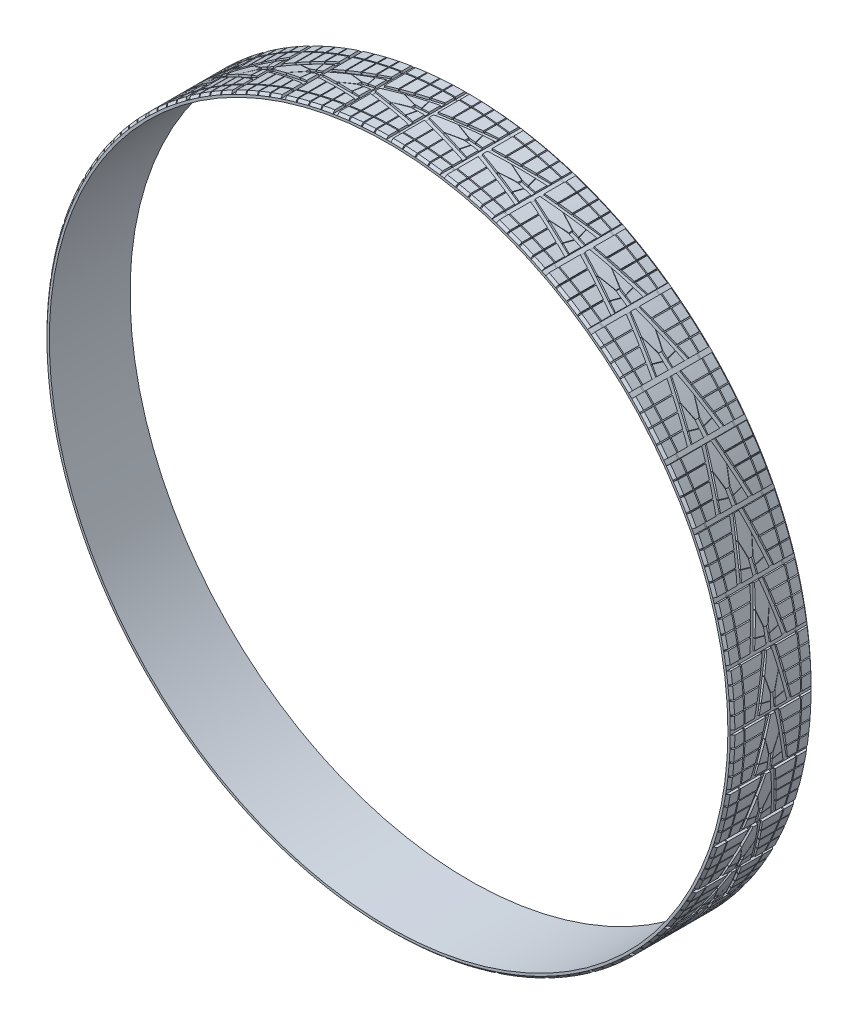
SolidWorks part; units mm, degrees
ref_plane "前视基准面" through (0, 0, 0) normal (0, 0, 1) x (1, 0, 0)
ref_plane "上视基准面" through (0, 0, 0) normal (0, 1, 0) x (1, 0, 0)
ref_plane "右视基准面" through (0, 0, 0) normal (1, 0, 0) x (0, 0, -1)
other "Configuration Table"
sketch "草图1" plane through (0, 0, 0) normal (0, 0, 1) x (1, 0, 0)
  circle A0 centre (0, 0) radius 147
  dimension "D1" = 294
extrude "拉伸-薄壁1" add sketch "草图1" along normal blind 35 thin
chamfer "倒角1" distance 1 angle 45 2 edges at (149, 0, 0) (149, 0, 35)
sketch "草图2" plane through (0, 0, 0) normal (0, 0, -1) x (-1, 0, 0)
  line L0 (0, 0) -> (0, 112.703) construction
  line L1 (-1, 148) -> (1, 148)
  line L2 (1, 148) -> (1, 150)
  line L3 (1, 150) -> (-1, 150)
  line L4 (-1, 150) -> (-1, 148)
  line L5 (22.4775, 148.3097) -> (22.1646, 146.3343)
  line L6 (22.1646, 146.3343) -> (24.14, 146.0214)
  line L7 (24.14, 146.0214) -> (24.4529, 147.9968)
  line L8 (24.4529, 147.9968) -> (22.4775, 148.3097)
  line L9 (45.4015, 142.9675) -> (44.7835, 141.0654)
  line L10 (44.7835, 141.0654) -> (46.6856, 140.4473)
  line L11 (46.6856, 140.4473) -> (47.3036, 142.3495)
  line L12 (47.3036, 142.3495) -> (45.4015, 142.9675)
  line L13 (67.2076, 134.105) -> (66.2996, 132.323)
  line L14 (66.2996, 132.323) -> (68.0816, 131.415)
  line L15 (68.0816, 131.415) -> (68.9896, 133.197)
  line L16 (68.9896, 133.197) -> (67.2076, 134.105)
  line L17 (87.3588, 121.9403) -> (86.1832, 120.3223)
  line L18 (86.1832, 120.3223) -> (87.8012, 119.1467)
  line L19 (87.8012, 119.1467) -> (88.9768, 120.7648)
  line L20 (88.9768, 120.7648) -> (87.3588, 121.9403)
  line L21 (105.3589, 106.7731) -> (103.9447, 105.3589)
  line L22 (103.9447, 105.3589) -> (105.3589, 103.9447)
  line L23 (105.3589, 103.9447) -> (106.7731, 105.3589)
  line L24 (106.7731, 105.3589) -> (105.3589, 106.7731)
  line L25 (120.7648, 88.9768) -> (119.1467, 87.8012)
  line L26 (119.1467, 87.8012) -> (120.3223, 86.1832)
  line L27 (120.3223, 86.1832) -> (121.9403, 87.3588)
  line L28 (121.9403, 87.3588) -> (120.7648, 88.9768)
  line L29 (133.197, 68.9896) -> (131.415, 68.0816)
  line L30 (131.415, 68.0816) -> (132.323, 66.2996)
  line L31 (132.323, 66.2996) -> (134.105, 67.2076)
  line L32 (134.105, 67.2076) -> (133.197, 68.9896)
  line L33 (142.3495, 47.3036) -> (140.4473, 46.6856)
  line L34 (140.4473, 46.6856) -> (141.0654, 44.7835)
  line L35 (141.0654, 44.7835) -> (142.9675, 45.4015)
  line L36 (142.9675, 45.4015) -> (142.3495, 47.3036)
  line L37 (147.9968, 24.4529) -> (146.0214, 24.14)
  line L38 (146.0214, 24.14) -> (146.3343, 22.1646)
  line L39 (146.3343, 22.1646) -> (148.3097, 22.4775)
  line L40 (148.3097, 22.4775) -> (147.9968, 24.4529)
  line L41 (150, 1) -> (148, 1)
  line L42 (148, 1) -> (148, -1)
  line L43 (148, -1) -> (150, -1)
  line L44 (150, -1) -> (150, 1)
  line L45 (148.3097, -22.4775) -> (146.3343, -22.1646)
  line L46 (146.3343, -22.1646) -> (146.0214, -24.14)
  line L47 (146.0214, -24.14) -> (147.9968, -24.4529)
  line L48 (147.9968, -24.4529) -> (148.3097, -22.4775)
  line L49 (142.9675, -45.4015) -> (141.0654, -44.7835)
  line L50 (141.0654, -44.7835) -> (140.4473, -46.6856)
  line L51 (140.4473, -46.6856) -> (142.3495, -47.3036)
  line L52 (142.3495, -47.3036) -> (142.9675, -45.4015)
  line L53 (134.105, -67.2076) -> (132.323, -66.2996)
  line L54 (132.323, -66.2996) -> (131.415, -68.0816)
  line L55 (131.415, -68.0816) -> (133.197, -68.9896)
  line L56 (133.197, -68.9896) -> (134.105, -67.2076)
  line L57 (121.9403, -87.3588) -> (120.3223, -86.1832)
  line L58 (120.3223, -86.1832) -> (119.1467, -87.8012)
  line L59 (119.1467, -87.8012) -> (120.7648, -88.9768)
  line L60 (120.7648, -88.9768) -> (121.9403, -87.3588)
  line L61 (106.7731, -105.3589) -> (105.3589, -103.9447)
  line L62 (105.3589, -103.9447) -> (103.9447, -105.3589)
  line L63 (103.9447, -105.3589) -> (105.3589, -106.7731)
  line L64 (105.3589, -106.7731) -> (106.7731, -105.3589)
  line L65 (88.9768, -120.7648) -> (87.8012, -119.1467)
  line L66 (87.8012, -119.1467) -> (86.1832, -120.3223)
  line L67 (86.1832, -120.3223) -> (87.3588, -121.9403)
  line L68 (87.3588, -121.9403) -> (88.9768, -120.7648)
  line L69 (68.9896, -133.197) -> (68.0816, -131.415)
  line L70 (68.0816, -131.415) -> (66.2996, -132.323)
  line L71 (66.2996, -132.323) -> (67.2076, -134.105)
  line L72 (67.2076, -134.105) -> (68.9896, -133.197)
  line L73 (47.3036, -142.3495) -> (46.6856, -140.4473)
  line L74 (46.6856, -140.4473) -> (44.7835, -141.0654)
  line L75 (44.7835, -141.0654) -> (45.4015, -142.9675)
  line L76 (45.4015, -142.9675) -> (47.3036, -142.3495)
  line L77 (24.4529, -147.9968) -> (24.14, -146.0214)
  line L78 (24.14, -146.0214) -> (22.1646, -146.3343)
  line L79 (22.1646, -146.3343) -> (22.4775, -148.3097)
  line L80 (22.4775, -148.3097) -> (24.4529, -147.9968)
  line L81 (1, -150) -> (1, -148)
  line L82 (1, -148) -> (-1, -148)
  line L83 (-1, -148) -> (-1, -150)
  line L84 (-1, -150) -> (1, -150)
  line L85 (-22.4775, -148.3097) -> (-22.1646, -146.3343)
  line L86 (-22.1646, -146.3343) -> (-24.14, -146.0214)
  line L87 (-24.14, -146.0214) -> (-24.4529, -147.9968)
  line L88 (-24.4529, -147.9968) -> (-22.4775, -148.3097)
  line L89 (-45.4015, -142.9675) -> (-44.7835, -141.0654)
  line L90 (-44.7835, -141.0654) -> (-46.6856, -140.4473)
  line L91 (-46.6856, -140.4473) -> (-47.3036, -142.3495)
  line L92 (-47.3036, -142.3495) -> (-45.4015, -142.9675)
  line L93 (-67.2076, -134.105) -> (-66.2996, -132.323)
  line L94 (-66.2996, -132.323) -> (-68.0816, -131.415)
  line L95 (-68.0816, -131.415) -> (-68.9896, -133.197)
  line L96 (-68.9896, -133.197) -> (-67.2076, -134.105)
  line L97 (-87.3588, -121.9403) -> (-86.1832, -120.3223)
  line L98 (-86.1832, -120.3223) -> (-87.8012, -119.1467)
  line L99 (-87.8012, -119.1467) -> (-88.9768, -120.7648)
  line L100 (-88.9768, -120.7648) -> (-87.3588, -121.9403)
  line L101 (-105.3589, -106.7731) -> (-103.9447, -105.3589)
  line L102 (-103.9447, -105.3589) -> (-105.3589, -103.9447)
  line L103 (-105.3589, -103.9447) -> (-106.7731, -105.3589)
  line L104 (-106.7731, -105.3589) -> (-105.3589, -106.7731)
  line L105 (-120.7648, -88.9768) -> (-119.1467, -87.8012)
  line L106 (-119.1467, -87.8012) -> (-120.3223, -86.1832)
  line L107 (-120.3223, -86.1832) -> (-121.9403, -87.3588)
  line L108 (-121.9403, -87.3588) -> (-120.7648, -88.9768)
  line L109 (-133.197, -68.9896) -> (-131.415, -68.0816)
  line L110 (-131.415, -68.0816) -> (-132.323, -66.2996)
  line L111 (-132.323, -66.2996) -> (-134.105, -67.2076)
  line L112 (-134.105, -67.2076) -> (-133.197, -68.9896)
  line L113 (-142.3495, -47.3036) -> (-140.4473, -46.6856)
  line L114 (-140.4473, -46.6856) -> (-141.0654, -44.7835)
  line L115 (-141.0654, -44.7835) -> (-142.9675, -45.4015)
  line L116 (-142.9675, -45.4015) -> (-142.3495, -47.3036)
  line L117 (-147.9968, -24.4529) -> (-146.0214, -24.14)
  line L118 (-146.0214, -24.14) -> (-146.3343, -22.1646)
  line L119 (-146.3343, -22.1646) -> (-148.3097, -22.4775)
  line L120 (-148.3097, -22.4775) -> (-147.9968, -24.4529)
  line L121 (-150, -1) -> (-148, -1)
  line L122 (-148, -1) -> (-148, 1)
  line L123 (-148, 1) -> (-150, 1)
  line L124 (-150, 1) -> (-150, -1)
  line L125 (-148.3097, 22.4775) -> (-146.3343, 22.1646)
  line L126 (-146.3343, 22.1646) -> (-146.0214, 24.14)
  line L127 (-146.0214, 24.14) -> (-147.9968, 24.4529)
  line L128 (-147.9968, 24.4529) -> (-148.3097, 22.4775)
  line L129 (-142.9675, 45.4015) -> (-141.0654, 44.7835)
  line L130 (-141.0654, 44.7835) -> (-140.4473, 46.6856)
  line L131 (-140.4473, 46.6856) -> (-142.3495, 47.3036)
  line L132 (-142.3495, 47.3036) -> (-142.9675, 45.4015)
  line L133 (-134.105, 67.2076) -> (-132.323, 66.2996)
  line L134 (-132.323, 66.2996) -> (-131.415, 68.0816)
  line L135 (-131.415, 68.0816) -> (-133.197, 68.9896)
  line L136 (-133.197, 68.9896) -> (-134.105, 67.2076)
  line L137 (-121.9403, 87.3588) -> (-120.3223, 86.1832)
  line L138 (-120.3223, 86.1832) -> (-119.1467, 87.8012)
  line L139 (-119.1467, 87.8012) -> (-120.7648, 88.9768)
  line L140 (-120.7648, 88.9768) -> (-121.9403, 87.3588)
  line L141 (-106.7731, 105.3589) -> (-105.3589, 103.9447)
  line L142 (-105.3589, 103.9447) -> (-103.9447, 105.3589)
  line L143 (-103.9447, 105.3589) -> (-105.3589, 106.7731)
  line L144 (-105.3589, 106.7731) -> (-106.7731, 105.3589)
  line L145 (-88.9768, 120.7648) -> (-87.8012, 119.1467)
  line L146 (-87.8012, 119.1467) -> (-86.1832, 120.3223)
  line L147 (-86.1832, 120.3223) -> (-87.3588, 121.9403)
  line L148 (-87.3588, 121.9403) -> (-88.9768, 120.7648)
  line L149 (-68.9896, 133.197) -> (-68.0816, 131.415)
  line L150 (-68.0816, 131.415) -> (-66.2996, 132.323)
  line L151 (-66.2996, 132.323) -> (-67.2076, 134.105)
  line L152 (-67.2076, 134.105) -> (-68.9896, 133.197)
  line L153 (-47.3036, 142.3495) -> (-46.6856, 140.4473)
  line L154 (-46.6856, 140.4473) -> (-44.7835, 141.0654)
  line L155 (-44.7835, 141.0654) -> (-45.4015, 142.9675)
  line L156 (-45.4015, 142.9675) -> (-47.3036, 142.3495)
  line L157 (-24.4529, 147.9968) -> (-24.14, 146.0214)
  line L158 (-24.14, 146.0214) -> (-22.1646, 146.3343)
  line L159 (-22.1646, 146.3343) -> (-22.4775, 148.3097)
  line L160 (-22.4775, 148.3097) -> (-24.4529, 147.9968)
  point P166 (0, 0)
  dimension "D1" = 1
  dimension "D2" = 1
  dimension "D3" = 148
  dimension "D5" = 150
  dimension "D4" = 40
extrude "切除-拉伸1" cut sketch "草图2" against normal through all
ref_plane "基准面1" through (0, 0, 5) normal (0, 0, 1) x (1, 0, 0)
sketch "草图3" plane through (0, 0, 5) normal (0, 0, 1) x (1, 0, 0)
  circle A0 centre (0, 0) radius 149
  circle A1 centre (0, 0) radius 148
  dimension "D1" = 296
  dimension "D2" = 298
extrude "切除-拉伸2" cut sketch "草图3" along normal blind 0.5
ref_plane "基准面2" through (0, 0, 30) normal (0, 0, 1) x (1, 0, 0)
sketch "草图4" plane through (0, 0, 30) normal (0, 0, 1) x (1, 0, 0)
  circle A0 centre (0, 0) radius 149
  circle A1 centre (0, 0) radius 148
  dimension "D1" = 298
extrude "切除-拉伸3" cut sketch "草图4" against normal blind 0.5
sketch3d "3D草图1"
  point P0 (148.5567, -11.4847, 15.2513)
ref_plane "基准面3" through (148.583, -11.1348, 0) normal (0.9972, -0.0747, 0) x (0.0747, 0.9972, 0)
sketch "草图5" plane through (148.583, -11.1348, 0) normal (0.9972, -0.0747, 0) x (0.0747, 0.9972, 0)
  line L0 (10.1373, 17.5) -> (-11.1671, 17.5) construction
  line L1 (10.1373, 5.5) -> (10.1373, 29.5) construction
  line L2 (-11.1671, 29.5) -> (-11.1671, 5.5) construction
  line L3 (-11.249, 25.5) -> (10.1373, 20.5)
  line L4 (-11.249, 29.5) -> (-11.249, 5.5) construction
  line L5 (10.1373, 20.5) -> (10.1373, 18.5)
  line L6 (10.1373, 18.5) -> (-11.249, 23.5)
  line L7 (-11.249, 23.5) -> (-11.249, 25.5)
  line L8 (10.1373, 16.5) -> (-11.249, 11.5)
  line L9 (10.1373, 14.5) -> (10.1373, 16.5)
  line L10 (-11.249, 9.5) -> (10.1373, 14.5)
  line L11 (-11.249, 11.5) -> (-11.249, 9.5)
  line L12 (-11.249, 18.5) -> (-5.249, 18.5)
  line L13 (-5.249, 18.5) -> (-5.249, 16.5)
  line L14 (-5.249, 16.5) -> (-11.249, 16.5)
  line L15 (-11.249, 18.5) -> (-11.249, 16.5)
  dimension "D1" = 2
  dimension "D2" = 1
  dimension "D3" = 6
  dimension "D4" = 1
  dimension "D5" = 6
extrude "切除-拉伸4" cut sketch "草图5" against normal mid plane 2
sketch "草图6" plane through (148.583, -11.1348, 0) normal (0.9972, -0.0747, 0) x (0.0747, 0.9972, 0)
  line L0 (-5.249, 18.5) -> (1.476, 20.525)
  line L1 (-11.2015, 23.4889) -> (10.0882, 18.5115) construction
  line L2 (1.476, 20.525) -> (1.6707, 20.4794)
  line L3 (10.1373, 18.5) -> (-11.249, 23.5) construction
  line L4 (1.6707, 20.4794) -> (-5.249, 18.3)
  line L5 (-5.249, 16.5) -> (-5.249, 18.5) construction
  line L6 (-5.249, 18.3) -> (-5.249, 18.5)
  line L7 (-11.2015, 17.5) -> (10.1373, 17.5) construction
  line L8 (-11.2015, 16.5) -> (-11.2015, 18.5) construction
  line L9 (10.1373, 16.5) -> (10.1373, 18.5) construction
  line L10 (-8.249, 18.5) -> (-7.3012, 22.577)
  line L11 (-11.249, 18.5) -> (-5.249, 18.5) construction
  line L12 (-7.3012, 22.577) -> (-7.1064, 22.5315)
  line L13 (-7.1064, 22.5315) -> (-8.049, 18.5)
  line L14 (-5.249, 18.5) -> (-11.2015, 18.5) construction
  line L15 (-8.049, 18.5) -> (-8.249, 18.5)
  line L16 (1.6707, 14.5206) -> (-5.249, 16.7)
  line L17 (1.476, 14.475) -> (1.6707, 14.5206)
  line L18 (-5.249, 16.5) -> (1.476, 14.475)
  line L19 (-5.249, 16.7) -> (-5.249, 16.5)
  line L20 (-7.1064, 12.4685) -> (-8.049, 16.5)
  line L21 (-7.3012, 12.423) -> (-7.1064, 12.4685)
  line L22 (-8.249, 16.5) -> (-7.3012, 12.423)
  line L23 (-8.049, 16.5) -> (-8.249, 16.5)
  line L25 (4.751, 35) -> (4.751, 21.7593)
  line L26 (11.0601, 35) -> (-12.1637, 35) construction
  line L28 (5.251, 35) -> (5.251, 21.6424)
  line L35 (-5.749, 35) -> (-5.749, 24.2141)
  line L36 (149, 35) -> (-149, 35) construction
  line L37 (10.0882, 20.5115) -> (-11.2015, 25.4889) construction
  line L38 (-5.749, 24.2141) -> (-6.249, 24.331)
  line L39 (-11.249, 25.5) -> (10.1373, 20.5) construction
  line L40 (-6.249, 24.331) -> (-6.249, 35)
  line L41 (-6.249, 35) -> (-5.749, 35)
  line L43 (-0.749, 35) -> (-0.749, 23.0452)
  line L44 (-0.749, 23.0452) -> (-0.249, 22.9283)
  line L45 (-0.249, 22.9283) -> (-0.249, 35)
  line L46 (-0.249, 35) -> (-0.749, 35)
  line L47 (-0.749, 11.9548) -> (-0.249, 12.0717)
  line L48 (-0.749, 0) -> (-0.749, 11.9548)
  line L49 (-0.249, 12.0717) -> (-0.249, 0)
  line L50 (-6.249, 10.669) -> (-6.249, 0)
  line L51 (-5.749, 10.7859) -> (-6.249, 10.669)
  line L52 (-5.749, 0) -> (-5.749, 10.7859)
  line L53 (-6.249, 0) -> (-5.749, 0)
  line L54 (-0.749, 0) -> (-0.249, 0)
  line L55 (4.751, 35) -> (5.251, 35)
  line L56 (4.751, 21.7593) -> (5.251, 21.6424)
  line L57 (-11.249, 34) -> (-11.249, 30) construction
  line L61 (4.751, 0) -> (4.751, 13.2407)
  line L62 (4.751, 0) -> (5.251, 0)
  line L63 (5.251, 0) -> (5.251, 13.3576)
  line L64 (4.751, 13.2407) -> (5.251, 13.3576)
  dimension "D1" = 0.2
  dimension "D2" = 0.2
  dimension "D3" = 0.2
  dimension "D4" = 0.2
  dimension "D5" = 0.5
  dimension "D6" = 5
  dimension "D7" = 5
  dimension "D8" = 0.5
  dimension "D9" = 0.5
  dimension "D10" = 5
extrude "切除-拉伸5" cut sketch "草图6" against normal mid plane 2
pattern_circular "阵列(圆周)1" count 40 over 360 about axis through (0, 0, 0) along (0, 0, 1) of "切除-拉伸4", "切除-拉伸5"
